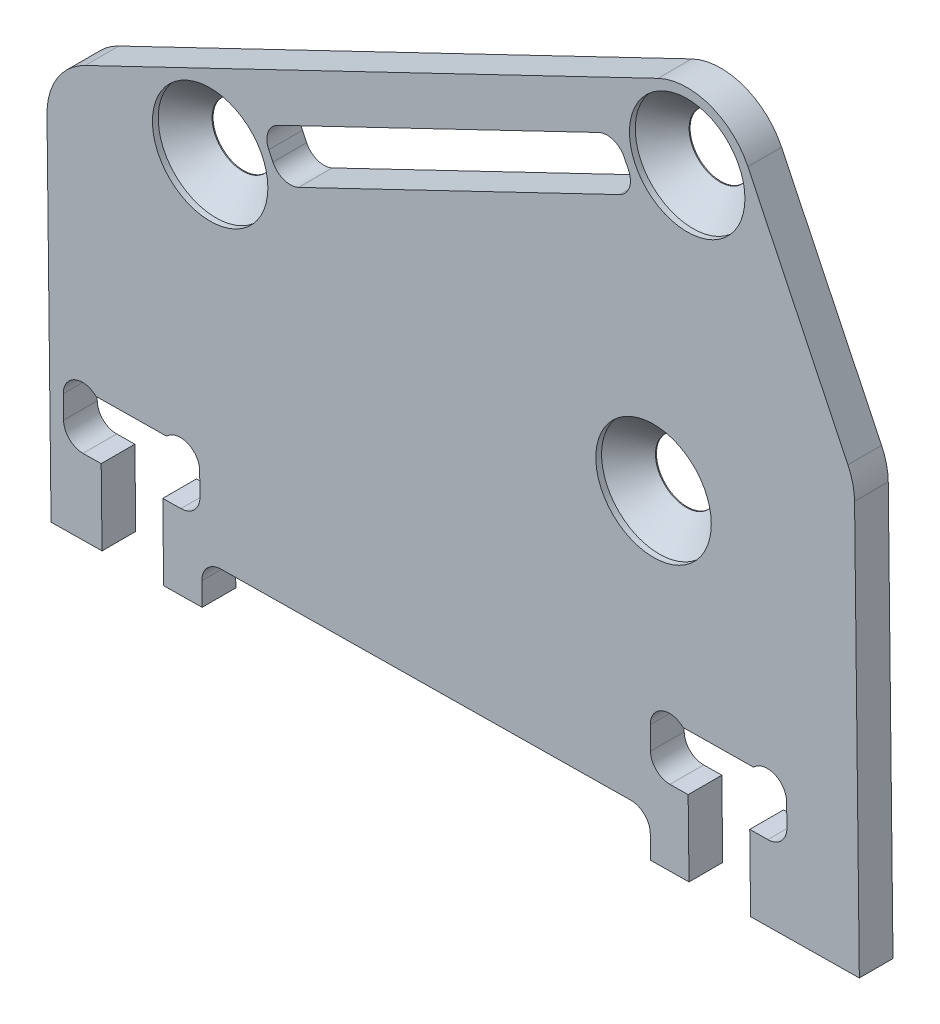
SolidWorks part; units mm, degrees
ref_plane "Front Plane" through (0, 0, 0) normal (0, 0, 1) x (1, 0, 0)
ref_plane "Top Plane" through (0, 0, 0) normal (0, 1, 0) x (1, 0, 0)
ref_plane "Right Plane" through (0, 0, 0) normal (1, 0, 0) x (0, 0, -1)
sketch "Sketch2" plane through (277.9441, -368.7823, 0) normal (0, 0, 1) x (0.9999, 0.0116, 0)
  line L0 (-273.6458, 371.9829) -> (-231.6458, 371.9829)
  line L1 (-237.0451, 403.462) -> (-231.9737, 392.5863)
  line L2 (-273.6458, 390.2567) -> (-231.6458, 390.2567) construction
  line L3 (-269.3958, 375.2829) -> (-238.8958, 375.2829) construction
  line L4 (-238.8958, 373.9829) -> (-238.8958, 371.9829) construction
  line L5 (-241.6964, 405.155) -> (-273.6458, 390.2567)
  line L6 (-273.6458, 390.2567) -> (-273.6458, 371.9829)
  line L7 (-242.1458, 376.5829) -> (-235.6458, 376.5829)
  line L8 (-265.1407, 390.3609) -> (-240.2172, 401.9829) construction
  line L9 (-260.534, 391.1298) -> (-243.7673, 398.9482)
  line L10 (-261.8629, 391.6135) -> (-262.0742, 392.0666)
  line L11 (-243.2836, 400.2771) -> (-243.4949, 400.7303)
  line L12 (-261.5905, 393.3955) -> (-244.8238, 401.214)
  line L13 (-261.4403, 390.7072) -> (-243.9175, 401.6366) construction
  line L14 (-270.1458, 388.0269) -> (-240.2172, 401.9829) construction
  line L15 (-242.861, 399.3708) -> (-262.4968, 392.9729) construction
  line L16 (-254.1458, 375.2829) -> (-254.1458, 371.9829) construction
  line L17 (-242.1458, 376.5829) -> (-242.1458, 373.9829)
  line L18 (-242.1458, 373.9829) -> (-235.6458, 373.9829)
  line L19 (-235.6458, 376.5829) -> (-235.6458, 373.9829)
  line L20 (-242.1458, 376.5829) -> (-235.6458, 373.9829) construction
  line L21 (-242.1458, 373.9829) -> (-235.6458, 376.5829) construction
  line L22 (-242.1458, 376.5829) -> (-239.5458, 373.9829) construction
  line L23 (-240.4958, 371.9829) -> (-237.2958, 371.9829)
  line L24 (-240.4958, 371.9829) -> (-240.4958, 373.9829)
  line L25 (-240.4958, 373.9829) -> (-237.2958, 373.9829)
  line L26 (-237.2958, 371.9829) -> (-237.2958, 373.9829)
  line L27 (-240.4958, 371.9829) -> (-237.2958, 373.9829) construction
  line L28 (-240.4958, 373.9829) -> (-237.2958, 371.9829) construction
  line L29 (-238.8958, 376.5829) -> (-238.8958, 373.9829) construction
  line L30 (-242.4387, 374.69) -> (-242.4387, 375.8758)
  line L31 (-235.3529, 375.8758) -> (-235.3529, 374.69)
  line L32 (-267.7958, 371.9829) -> (-267.7958, 373.9829)
  line L33 (-270.9958, 371.9829) -> (-270.9958, 373.9829)
  line L34 (-266.1458, 373.9829) -> (-272.6458, 373.9829)
  line L35 (-272.9387, 375.8758) -> (-272.9387, 374.69)
  line L36 (-266.1458, 376.5829) -> (-272.6458, 376.5829)
  line L37 (-265.8529, 374.69) -> (-265.8529, 375.8758)
  line L38 (-241.4387, 373.69) -> (-236.3529, 373.69)
  line L39 (-231.6458, 391.1072) -> (-231.6458, 371.9829)
  line L40 (-266.8529, 373.69) -> (-271.9387, 373.69)
  line L41 (-265.7958, 369.7829) -> (-242.4958, 369.7829) construction
  line L42 (-270.9958, 371.9829) -> (-273.6458, 371.9829)
  line L43 (-270.9958, 371.9829) -> (-270.9958, 369.7829)
  line L44 (-270.9958, 369.7829) -> (-273.6458, 369.7829)
  line L45 (-273.6458, 371.9829) -> (-273.6458, 369.7829)
  line L46 (-231.6458, 371.9829) -> (-237.2958, 371.9829)
  line L47 (-231.6458, 371.9829) -> (-231.6458, 369.7829)
  line L48 (-231.6458, 369.7829) -> (-237.2958, 369.7829)
  line L49 (-237.2958, 371.9829) -> (-237.2958, 369.7829)
  line L50 (-267.7958, 371.9829) -> (-265.7958, 371.9829)
  line L51 (-267.7958, 371.9829) -> (-267.7958, 369.7829)
  line L52 (-267.7958, 369.7829) -> (-265.7958, 369.7829)
  line L53 (-265.7958, 371.9829) -> (-265.7958, 369.7829)
  line L54 (-240.4958, 371.9829) -> (-242.4958, 371.9829)
  line L55 (-240.4958, 371.9829) -> (-240.4958, 369.7829)
  line L56 (-240.4958, 369.7829) -> (-242.4958, 369.7829)
  line L57 (-242.4958, 371.9829) -> (-242.4958, 369.7829)
  line L58 (-265.7958, 371.9829) -> (-263.5958, 369.7829) construction
  line L59 (-254.1458, 371.9829) -> (-254.1458, 369.7829) construction
  circle A0 centre (-242.1458, 386.4829) radius 1.6
  circle A1 centre (-265.1407, 390.3609) radius 1.6
  circle A2 centre (-240.2172, 401.9829) radius 1.6
  circle A3 centre (-270.1458, 388.0269) radius 3.5
  circle A4 centre (-240.2172, 401.9829) radius 3.5
  arc A5 (-262.0742, 392.0666) -> (-261.5905, 393.3955) centre (-261.1679, 392.4892) cw
  circle A6 centre (-235.1458, 391.1072) radius 3.5
  circle A7 centre (-241.4387, 375.8758) radius 1
  circle A8 centre (-236.3529, 375.8758) radius 1
  circle A9 centre (-236.3529, 374.69) radius 1
  circle A10 centre (-241.4387, 374.69) radius 1
  arc A11 (-261.8629, 391.6135) -> (-260.534, 391.1298) centre (-260.9566, 392.0361) ccw
  arc A12 (-243.7673, 398.9482) -> (-243.2836, 400.2771) centre (-244.1899, 399.8545) ccw
  circle A13 centre (-271.9387, 374.69) radius 1
  circle A14 centre (-271.9387, 375.8758) radius 1
  circle A15 centre (-266.8529, 375.8758) radius 1
  circle A16 centre (-266.8529, 374.69) radius 1
  arc A17 (-243.4949, 400.7303) -> (-244.8238, 401.214) centre (-244.4012, 400.3077) ccw
  circle A18 centre (-265.0887, 371.2758) radius 1
  circle A19 centre (-243.2029, 371.2758) radius 1
  point P10 (-252.6789, 396.1719)
  point P15 (-240.2172, 401.9829)
  point P21 (-238.8958, 372.9829)
  dimension "D1" = 3.2
  dimension "D10" = 3.2
  dimension "D13" = 20.5
  dimension "D2" = 7
  dimension "D17" = 1
  dimension "D11" = 45
  dimension "D14" = 2
  dimension "D3" = 30
  dimension "D4" = 12
  dimension "D5" = 30.5
  dimension "D6" = 4.25
  dimension "D7" = 6.5
  dimension "D8" = 2.6
  dimension "D9" = 2
  dimension "D12" = 2.5
  dimension "D15" = 25
  dimension "D16" = 14.5
  dimension "D18" = 12
  dimension "D19" = 42
  dimension "D20" = 2.2
  dimension "D21" = 2
  dimension "D22" = 45
extrude "Base shape" add sketch "Sketch2" along normal blind 1.75 contours L45 L6 | A17 L11 A4 L5 A3 L6 L0 L33 L40 A13 L35 A14 L36 A15 L37 A16 L32 L24 L38 A10 L30 A7 L7 A8 L31 A9 L26 L39 A6 L1 A12 L9 A11 L10 A5 | A3 | A4 A2 | A6 | L0 L45 L44 L43 | L53 L0 L51 L52 | L0 L57 L56 L55 | L0 L49 L48 L47 | L53 A18 | L0 A18 | A19 L0 | A19 L57 region at (22.3566, 12.8576, 0) region at (1.3377, -1.0845, 0) region at (3.3136, 16.0836, 0) region at (6.8015, -1.0484, 0) region at (8.5552, 0.2181, 0) region at (7.7389, -0.6173, 0) region at (34.2042, 33.5951, 0) region at (30.4395, 0.472, 0) region at (38.2755, 19.5698, 0) region at (31.2749, -0.3442, 0) region at (32.222, -0.7534, 0) region at (39.1851, -0.6453, 0)
sketch "Sketch3" plane through (0, 0, 1.75) normal (0, 0, 1) x (1, 0, 0)
  circle A0 centre (8.2913, 18.4755) radius 3
  circle A1 centre (31.3296, 14.8646) radius 3
  circle A2 centre (33.0782, 30.3859) radius 3
  dimension "D1" = 6
extrude "Right insets" cut sketch "Sketch3" against normal blind 0.3
chamfer "Right chamfers" distance 1.4 angle 45 3 edges at (9.8913, 18.4755, 1.45) (32.9296, 14.8646, 1.45) (34.6782, 30.3859, 1.45)
fillet "Milling fillets" radius 1 2 edges at (31.1479, 0.3615, 0.875) (7.8495, 0.0911, 0.875)
sketch "Sketch4" [suppressed] plane through (0, 0, 0) normal (0, 0, -1) x (-1, 0, 0)
  circle A0 centre (-33.0782, 30.3859) radius 3
  circle A1 centre (-8.2913, 18.4755) radius 3
  circle A2 centre (-31.3296, 14.8646) radius 3
  dimension "D1" = 6
extrude "Left insets" [suppressed] cut sketch "Sketch4" against normal blind 0.3
chamfer "Left chamfers" [suppressed] distance 1.4 angle 45
